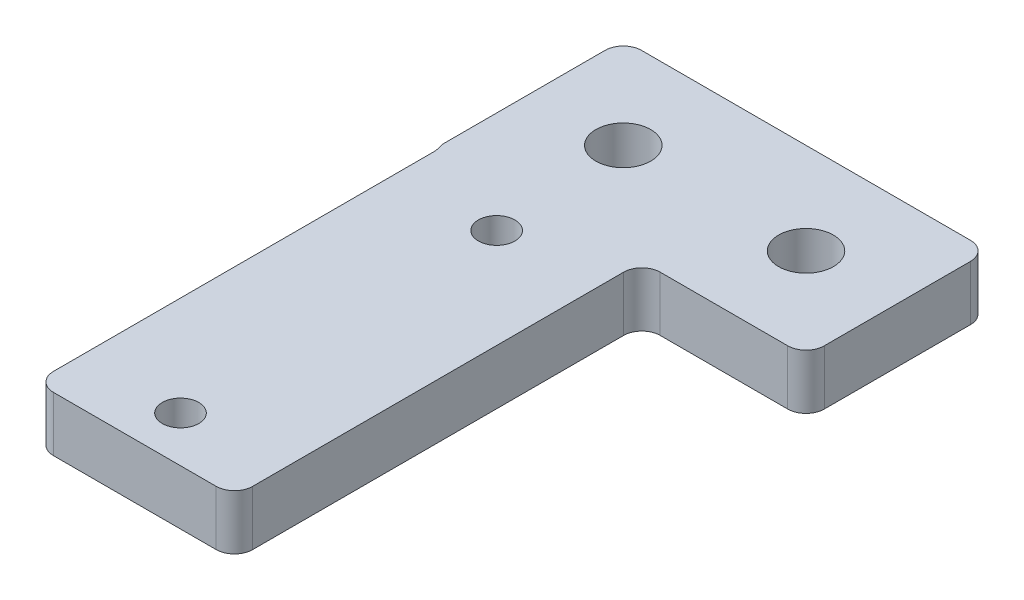
SolidWorks part; units mm, degrees
ref_plane "Front Plane" through (0, 0, 0) normal (0, 0, 1) x (1, 0, 0)
ref_plane "Top Plane" through (0, 0, 0) normal (0, 1, 0) x (1, 0, 0)
ref_plane "Right Plane" through (0, 0, 0) normal (1, 0, 0) x (0, 0, -1)
sketch "Sketch1" plane through (0, 0, 0) normal (0, 1, 0) x (1, 0, 0)
  line L0 (11.02, 0) -> (20, 0)
  line L1 (0, 0) -> (0.12, 0)
  line L2 (0, 0) -> (0, 10)
  line L3 (0, 10) -> (20, 10)
  line L4 (20, 0) -> (20, 10)
  line L6 (0.12, 0) -> (0.12, -22.3)
  line L7 (0.12, -22.3) -> (11.02, -22.3)
  line L8 (11.02, 0) -> (11.02, -22.3)
  circle A0 centre (5, 5) radius 1.5
  circle A1 centre (15, 5) radius 1.5
  circle A2 centre (5.57, -2.5) radius 1
  circle A3 centre (5.57, -19.8) radius 1
  dimension "D3" = 3
  dimension "D4" = 3
  dimension "D12" = 2
  dimension "D13" = 2
  dimension "D1" = 20
  dimension "D2" = 10
  dimension "D5" = 5
  dimension "D6" = 5
  dimension "D7" = 5
  dimension "D8" = 5
  dimension "D9" = 2.5
  dimension "D10" = 5.45
  dimension "D11" = 0.57
  dimension "D14" = 2.5
  dimension "D15" = 22.3
  dimension "D18" = 5.45
extrude "Boss-Extrude1" add sketch "Sketch1" along normal blind 3 contours L1 L0 L4 L3 L2 A1 A0 region at (7.5181, 0, 4.0479)
fillet "Fillet2" radius 1 6 edges at (0, 1.5, -10) (20, 1.5, -10) (11.02, 1.5, 0) (20, 1.5, 0) (0.12, 1.5, 22.3) (11.02, 1.5, 22.3)
fillet "Fillet5" radius 1 1 edges at (0.12, 1.5, 0)
fillet "Fillet6" radius 1 1 edges at (0, 1.5, 0)
move or copy body "Body-Move/Copy1" [suppressed] bodies to move or copy 102
